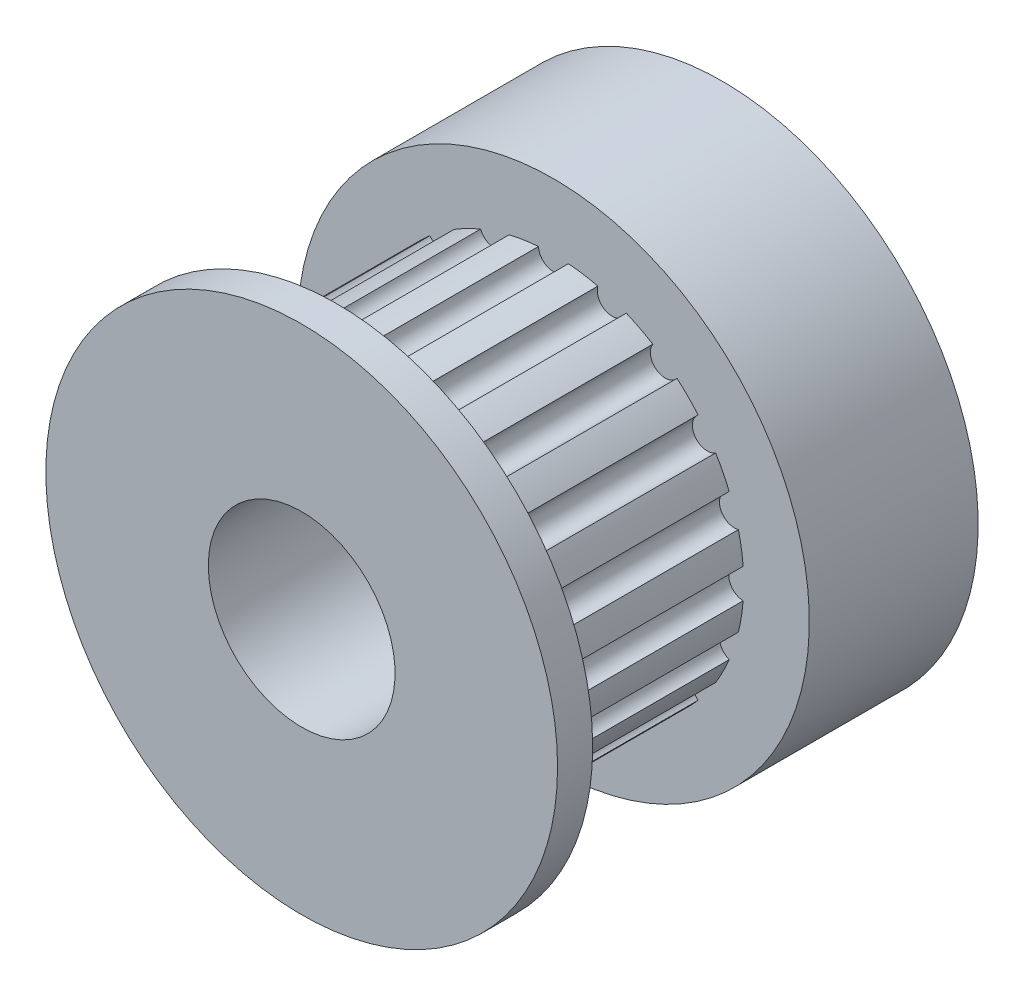
SolidWorks part; units mm, degrees
ref_plane "Plan de face" through (0, 0, 0) normal (0, 0, 1) x (1, 0, 0)
ref_plane "Plan de dessus" through (0, 0, 0) normal (0, 1, 0) x (1, 0, 0)
ref_plane "Plan de droite" through (0, 0, 0) normal (1, 0, 0) x (0, 0, -1)
sketch "Sketch1" plane through (0, 0, 0) normal (0, 0, 1) x (1, 0, 0)
  circle A0 centre (0, 0) radius 8.6995
  dimension "D1" = 17.399
extrude "Boss-Extrude1" add sketch "Sketch1" along normal blind 5.7404
sketch "Sketch2" plane through (0, 0, 5.7404) normal (0, 0, 1) x (1, 0, 0)
  circle A0 centre (0, 0) radius 6.4681
  dimension "D1" = 12.9361
extrude "Boss-Extrude2" add sketch "Sketch2" along normal blind 7.366
sketch "Sketch3" plane through (0, 0, 13.1064) normal (0, 0, 1) x (1, 0, 0)
  line L0 (0, -55) -> (0, 55) construction
  circle A0 centre (0, 6.4681) radius 0.508
  circle A1 centre (0, 0) radius 6.4681 construction
  dimension "D1" = 1.016
extrude "Cut-Extrude1" cut sketch "Sketch3" against normal up to surface (7.366 mm away) up to face at (6.4681, 0, 5.7404)
pattern_circular "CirPattern1" count 20 over 360 about axis through (0, 0, 13.1064) along (0, 0, 1) of "Cut-Extrude1"
sketch "Sketch4" plane through (0, 0, 13.1064) normal (0, 0, 1) x (1, 0, 0)
  circle A0 centre (0, 0) radius 8.6995
  dimension "D1" = 17.399
extrude "Boss-Extrude3" add sketch "Sketch4" along normal blind 1.1938
sketch "Sketch5" plane through (0, 0, 0) normal (0, 0, -1) x (-1, 0, 0)
  circle A0 centre (0, 0) radius 3.175
  dimension "D1" = 6.35
extrude "Cut-Extrude2" cut sketch "Sketch5" against normal through all
sketch "Sketch6" plane through (0, 0, 0) normal (0, 0, -1) x (-1, 0, 0)
  circle A0 centre (0, 0) radius 8.6995
